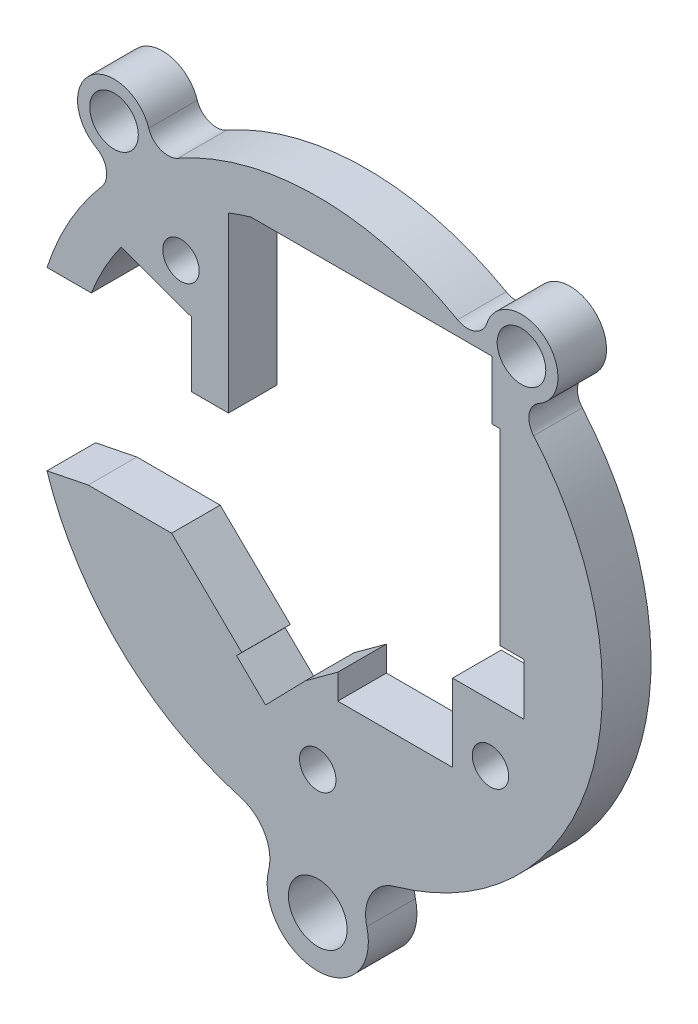
SolidWorks part; units mm, degrees
ref_plane "Front Plane" through (0, 0, 0) normal (0, 0, 1) x (1, 0, 0)
ref_plane "Top Plane" through (0, 0, 0) normal (0, 1, 0) x (1, 0, 0)
ref_plane "Right Plane" through (0, 0, 0) normal (1, 0, 0) x (0, 0, -1)
sketch "Sketch1" plane through (0, 0, 0) normal (0, 0, 1) x (1, 0, 0)
  line L1 (-14.9521, -2.9485) -> (-16.9841, -2.9485)
  line L2 (-16.9841, 2.9485) -> (-16.9841, 5.5245)
  line L3 (-14.9521, 2.9485) -> (-16.9841, 2.9485)
  line L4 (-16.9841, 5.5245) -> (-21.1739, 5.5245)
  line L5 (-16.9841, -2.9485) -> (-16.9841, -5.5245)
  line L6 (-16.9841, -5.5245) -> (-20.8712, -5.5245)
  line L7 (-15.24, 0) -> (-21.59, 0) construction
  line B0 (-15.24, 18.2372) -> (15.24, 18.2372)
  line B1 (11.43, 14.6558) -> (11.43, -0.8128)
  line B2 (0, 18.2372) -> (0, 0) construction
  line B3 (-5.6007, 14.1736) -> (-5.6007, -0.8128)
  line B4 (11.43, 14.6558) -> (-4.1791, 14.6558)
  line B5 (-5.6007, -0.8128) -> (11.43, -0.8128)
  line B6 (8.4582, -4.064) -> (12.9413, -4.064)
  line B7 (11.43, -0.8128) -> (12.9413, -0.8128)
  line B8 (12.9413, -0.8128) -> (12.9413, -4.064)
  line B9 (8.4582, -7.3406) -> (1.2573, -7.3406)
  line B10 (8.4582, -4.064) -> (8.4582, -7.3406)
  line B11 (-4.3942, -0.8128) -> (-4.3942, -4.064)
  line B12 (-4.3942, -4.064) -> (1.2573, -4.064)
  line B13 (1.2573, -4.064) -> (1.2573, -7.3406)
  line B14 (-0.7747, -8.8265) -> (-3.2737, -11.3919)
  line B15 (-0.7747, -8.8265) -> (-2.5941, -7.0541)
  line B16 (-2.5941, -7.0541) -> (-2.9176, -7.3862)
  line B17 (-2.9176, -7.3862) -> (-8.5123, -1.9362)
  line B18 (-8.5123, -1.9362) -> (-10.3645, -3.8375)
  line B19 (-10.3645, -3.8375) -> (-4.7697, -9.2875)
  line B20 (-4.7697, -9.2875) -> (-5.0932, -9.6195)
  line B21 (-5.0932, -9.6195) -> (-3.2737, -11.3919)
  line B22 (-12.3326, 18.2372) -> (-12.3326, 8.9535)
  line B23 (-7.9248, 18.2372) -> (-7.9248, 7.366) construction
  line B24 (-12.3326, 8.9535) -> (-7.9248, 7.366)
  line B25 (-5.6007, 3.302) -> (-7.9248, 3.302)
  line B26 (-7.9248, 3.302) -> (-7.9248, 7.366)
  line B27 (-14.3951, -5.0038) -> (-9.1672, -5.0038)
  line B28 (-0.7747, -8.8265) -> (1.2573, -7.3406)
  arc B29 (-3.302, 14.878) -> (3.302, 14.878) centre (0, 0) ccw
  circle B30 centre (0, -18.415) radius 1.4224
  circle B31 centre (0, 18.415) radius 1.4224
  circle B32 centre (0, 0) radius 21.59
  line B33 (1.2573, -8.9154) -> (8.4582, -8.9154)
  line B34 (1.2573, -7.3406) -> (1.2573, -8.9154)
  line B35 (8.4582, -7.3406) -> (8.4582, -8.9154)
  dimension "D1" = 2.032
  dimension "D2" = 11.049
sketch_block_instance "Block1-1"
sketch_block "Block1" parameters "D1"=3.81, "D2"=30.48, "D3"=3.5814, "D4"=9.6393, "D5"=19.05, "D6"=22.3012, "D7"=1.5113, "D8"=4.4831, "D9"=6.5278, "D10"=7.2009, "D11"=5.6515, "D12"=27.0637, "D13"=29.6291, "D14"=3.5814, "D15"=14.4653, "D16"=2.54, "D17"=2.6543, "D18"=10.3505, "D19"=9.2837, "D20"=10.8712, "D21"=7.3152, "D22"=14.9352, "D23"=23.241
extrude "Boss-Extrude1" add sketch "Sketch1" along normal blind 3.048 contours B0 B32 B29 B4 B1 B31 B30 | B27 B29 B1 B7 B8 B6 B10 B9 B28 B14 B21 B20 B19 | B3 B29 B24 B26 B25 | B0 B32 B31 | B22 B32 L4 L2 L3 B29 region at (-15.2714, -4.1381, 0) region at (-15.71, 9.7203, 0) region at (-11.7811, -5.3936, 0) region at (-7.7282, 8.9883, 0) region at (0, 21.3565, 0)
sketch "Sketch2" plane through (0, 0, 3.048) normal (0, 0, 1) x (1, 0, 0)
  line L0 (-14.3951, -5.0038) -> (-16.9841, -5.5245)
  line L2 (-16.9841, 5.5245) -> (-14.2034, 5.5245)
  line L3 (-14.3951, -5.0038) -> (-14.2034, 5.5245)
  line L4 (-16.9841, -5.5245) -> (-16.9841, 5.5245)
  arc A0 (-12.3326, 8.9535) -> (-14.9521, 2.9485) centre (0, 0) ccw construction
extrude "Cut-Extrude1" cut sketch "Sketch2" against normal through all
sketch "Sketch3" plane through (0, 0, 3.048) normal (0, 0, 1) x (1, 0, 0)
  line L0 (0, 0) -> (11.43, 14.6558) construction
  line L1 (0, 0) -> (-14.0833, 10.9835) construction
  line L2 (0, 0) -> (-10.9835, -14.0833) construction
  line L3 (0, 0) -> (14.0833, -10.9835) construction
  circle A0 centre (0, 0) radius 17.86
  circle A1 centre (0, 0) radius 21.59
extrude "Cut-Extrude2" cut sketch "Sketch3" against normal through all
sketch "Sketch4" plane through (0, 0, 3.048) normal (0, 0, 1) x (1, 0, 0)
  line L0 (0, -21.035) -> (0, 0) construction
  line L6 (10.2071, 14.6558) -> (11.43, 14.6558)
  line L7 (11.43, 14.6558) -> (11.43, 13.7235)
  line L19 (-21.6223, 17.86) -> (27.8478, 17.86) construction
  circle A0 centre (0, 0) radius 17.86
  circle A1 centre (12.7793, 15.574) radius 1.524
  circle A2 centre (-12.7793, 15.574) radius 2.286
  circle A3 centre (12.7793, 15.574) radius 2.286
  circle A4 centre (-14.5094, 12.4672) radius 1.27
  circle A5 centre (-9.3946, 16.6642) radius 1.27
  circle A6 centre (-12.7793, 15.574) radius 1.524
  circle A7 centre (0, -21.035) radius 1.8415
  circle A8 centre (0, -21.035) radius 3.175
  circle A9 centre (9.3946, 16.6642) radius 1.27
  circle A11 centre (14.5094, 12.4672) radius 1.27
  arc A12 (-1.2889, 17.8134) -> (1.2889, 17.8134) centre (0, 18.415) ccw
  arc A13 (-1.2889, 17.8134) -> (1.2889, 17.8134) centre (0, 18.415) ccw construction
  circle A14 centre (5.5404, -19.6332) radius 2.54
  circle A15 centre (-5.5404, -19.6332) radius 2.54
  arc M3 (-1.2889, -17.8134) -> (1.2889, -17.8134) centre (0, -18.415) cw
  arc M4 (1.2889, -17.8134) -> (11.43, 13.7235) centre (0, 0) ccw
  dimension "D2" = 3.048
  dimension "D4" = 2.54
  dimension "D3" = 3.683
  dimension "D1" = 4.572
  dimension "D5" = 6.35
  dimension "D6" = 5.08
extrude "Boss-Extrude3" add sketch "Sketch4" against normal blind 3.048 contours A5 A2 A0 | A2 A6 | A4 A0 A2 | A0 A12 | A9 A0 L6 A3 | L7 A3 L6 A1 | A11 A3 L7 A0 | A8 A7 | A15 A8 A0 | A14 A0 A8 M4 | A0 M3 region at (10.0871, 15.2114, 3.048) region at (10.5609, 15.4611, 3.048) region at (12.8284, 12.9196, 3.048) region at (0, 17.4932, 3.048) region at (-10.1667, 15.1037, 3.048) region at (2.6103, -18.2487, 3.048) region at (-12.8282, 12.9198, 3.048) region at (-12.5808, 13.3615, 3.048) region at (0, -17.4932, 3.048) region at (3.0615, -20.6537, 3.048) region at (-2.6103, -18.2487, 3.048)
sketch "Sketch7" plane through (0, 0, 3.048) normal (0, 0, 1) x (1, 0, 0)
  line L1 (11.43, 14.6558) -> (10.922, 14.6558)
  line L2 (11.43, 14.6558) -> (11.43, 10.9728)
  line L3 (11.43, 10.9728) -> (10.922, 10.9728)
  line L4 (10.922, 14.6558) -> (10.922, 10.9728)
  dimension "D1" = 0.508
  dimension "D2" = 3.683
extrude "Boss-Extrude4" add sketch "Sketch7" against normal up to vertex (3.048 mm away) up to point (11.43, 14.6558, 0)
sketch "Sketch8" plane through (0, 0, 3.048) normal (0, 0, 1) x (1, 0, 0)
  line L0 (-15.24, 18.2372) -> (15.24, 18.2372) construction
  line L1 (-15.24, 18.2372) -> (15.24, 18.2372)
  line L2 (0, 18.2372) -> (0, -12.1158) construction
  line L3 (10.8325, 18.2372) -> (10.8325, -6.5024) construction
  line L4 (0, 0) -> (14.5917, -10.2986) construction
  line L5 (-8.579, 11.2522) -> (-8.579, 18.2372) construction
  circle A0 centre (0, -13.2588) radius 1.143
  circle A1 centre (10.8325, -7.6454) radius 1.143
  arc A2 (4.8506, -17.1887) -> (13.5462, 11.6395) centre (0, 0) ccw construction
  circle A3 centre (-8.579, 10.1092) radius 1.143
  circle A4 centre (0, 0) radius 15.2591 construction
  circle A5 centre (0, 0) radius 13.2588 construction
  dimension "D2" = 2.286
  dimension "D4" = 6.985
  dimension "D5" = 30.5181
  dimension "D1" = 30.353
  dimension "D3" = 24.7396
extrude "Cut-Extrude3" cut sketch "Sketch8" against normal through all contours A0 | A1 | A3 region at (0, -13.2588, 3.048) region at (10.8325, -7.6454, 3.048) region at (-8.579, 10.1092, 3.048)
sketch "Sketch9" plane through (0, 0, 3.048) normal (0, 0, 1) x (1, 0, 0)
  line B0 (-12.3326, 8.9535) -> (-7.9248, 7.366)
  line B1 (-7.9248, 3.302) -> (-7.9248, 7.366)
  line B2 (-14.2034, 5.5245) -> (-16.9841, 5.5245)
  line B3 (-16.9841, -5.5245) -> (-14.3951, -5.0038)
  line B4 (-14.3951, -5.0038) -> (-9.1672, -5.0038)
  line B5 (-9.1672, -5.0038) -> (-4.7697, -9.2875)
  line B6 (-4.7697, -9.2875) -> (-5.0932, -9.6195)
  line B7 (-5.0932, -9.6195) -> (-3.2737, -11.3919)
  line B8 (-0.7747, -8.8265) -> (-3.2737, -11.3919)
  line B9 (-0.7747, -8.8265) -> (1.2573, -7.3406)
  line B10 (1.2573, -7.3406) -> (1.2573, -8.9154)
  line B11 (1.2573, -8.9154) -> (8.4582, -8.9154)
  line B12 (8.4582, -4.064) -> (8.4582, -8.9154)
  line B13 (8.4582, -4.064) -> (12.9413, -4.064)
  line B14 (12.9413, -0.8128) -> (12.9413, -4.064)
  line B15 (11.43, -0.8128) -> (12.9413, -0.8128)
  line B16 (11.43, 10.9728) -> (11.43, -0.8128)
  line B17 (10.922, 10.9728) -> (11.43, 10.9728)
  line B18 (10.922, 14.6558) -> (10.922, 10.9728)
  line B19 (-4.1791, 14.6558) -> (10.922, 14.6558)
  line B20 (-5.6007, 14.1736) -> (-5.6007, 3.302)
  line B21 (-5.6007, 3.302) -> (-7.9248, 3.302)
  circle B22 centre (-8.579, 10.1092) radius 1.143
  arc B23 (-12.3326, 8.9535) -> (-14.2034, 5.5245) centre (0, 0) ccw
  arc B24 (-4.1791, 14.6558) -> (-5.6007, 14.1736) centre (0, 0) ccw
  circle B25 centre (10.8325, -7.6454) radius 1.143
  circle B26 centre (0, -13.2588) radius 1.143
sketch_block_instance "Block2-1"
sketch_block "Block2"
